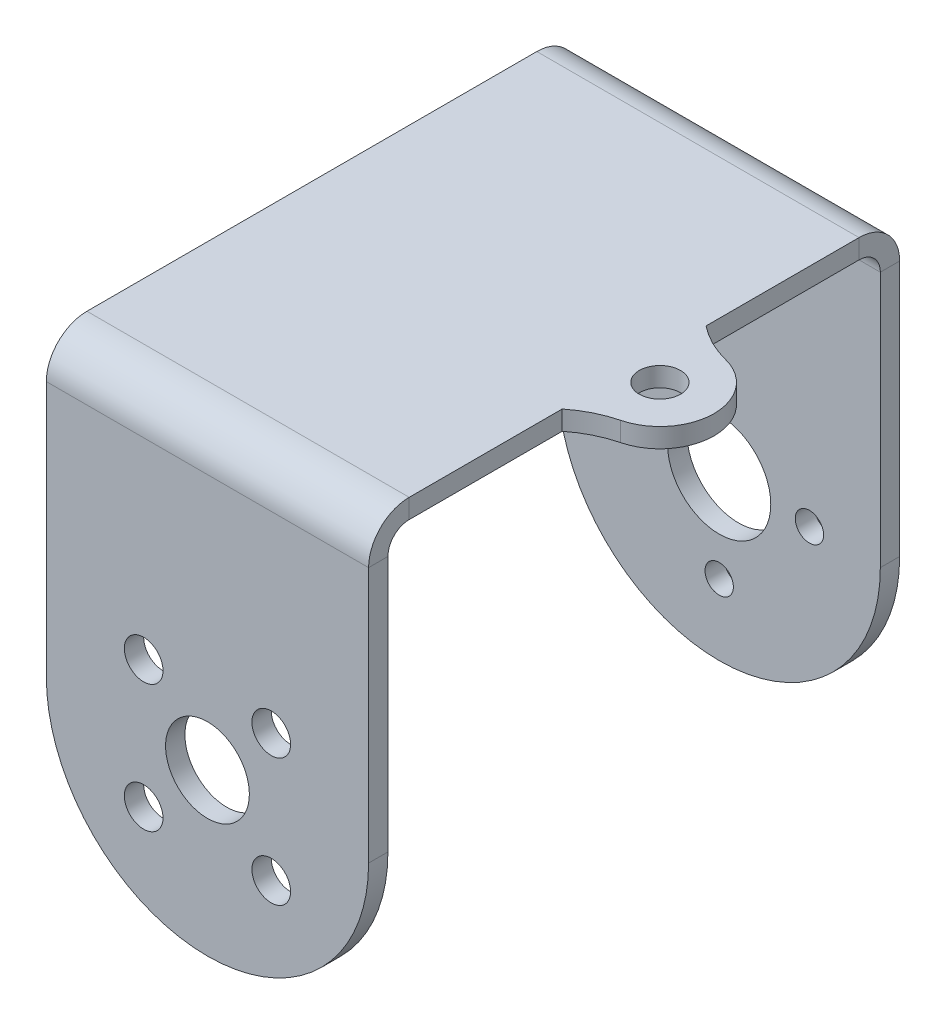
SolidWorks part; units mm, degrees
note: The reader was unsure of these and kept them because the rebuilt part matched: flange length of "Edge-Flange1".
material "1.0037 (S235JR)"
ref_plane "Front Plane" through (0, 0, 0) normal (0, 0, 1) x (1, 0, 0)
ref_plane "Top Plane" through (0, 0, 0) normal (0, 1, 0) x (1, 0, 0)
ref_plane "Right Plane" through (0, 0, 0) normal (1, 0, 0) x (0, 0, -1)
sketch "Sketch1" plane through (0, 0, 0) normal (0, 1, 0) x (1, 0, 0)
  line L1 (12.5, -19.1) -> (-12.5, -19.1)
  line L2 (12.5, -19.1) -> (12.5, 19.1)
  line L3 (12.5, 19.1) -> (-12.5, 19.1)
  line L4 (-12.5, -19.1) -> (-12.5, 19.1)
  line L5 (12.5, -19.1) -> (-12.5, 19.1) construction
  line L6 (12.5, 19.1) -> (-12.5, -19.1) construction
  point P0 (0, 0)
  dimension "D1" = 38.2
  dimension "D2" = 25
base flange "Base-Flange1" sketch "Sketch1" thickness 1.5 reverse thickness direction no parameters "D1"=1.65
edge flange "Edge-Flange1" sketch "Sketch10" flange profiles "Sketch10", "Sketch11" flange angle 90 flange length 34 flange position material outside bend radius 1.65 thickness 1.5 relief rectangular parameters "D6"=10, "D8"=1
sketch "Sketch10" plane through (0, -1.5, 19.1) normal (0, 0, 1) x (-1, 0, 0)
  line L0 (12.5, 0) -> (-12.5, 0) construction
  line L1 (12.5, 0) -> (-12.5, 0)
  line L2 (-12.5, 0) -> (-12.5, 34)
  line L3 (-12.5, 34) -> (12.5, 34)
  line L4 (12.5, 34) -> (12.5, 0)
sketch "Sketch11" plane through (0, -1.5, -19.1) normal (0, 0, -1) x (1, 0, 0)
  line L0 (12.5, 0) -> (-12.5, 0) construction
  line L1 (12.5, 0) -> (-12.5, 0)
  line L2 (-12.5, 0) -> (-12.5, 34)
  line L3 (-12.5, 34) -> (12.5, 34)
  line L4 (12.5, 34) -> (12.5, 0)
bend "EdgeBend1" bend radius 1.65 bend angle 90 parameters "D5"=1
bend "EdgeBend2" bend radius 1.65 bend angle 90 parameters "D5"=2
sketch "Sketch12" plane through (0, 0, 20.6) normal (0, 0, 1) x (1, 0, 0)
  line L0 (-12.5, -35.5) -> (12.5, -35.5) construction
  line L1 (4.9497, -27.9497) -> (-4.9497, -27.9497) construction
  line L2 (4.9497, -27.9497) -> (4.9497, -18.0503) construction
  line L3 (4.9497, -18.0503) -> (-4.9497, -18.0503) construction
  line L4 (-4.9497, -27.9497) -> (-4.9497, -18.0503) construction
  line L5 (4.9497, -27.9497) -> (-4.9497, -18.0503) construction
  line L6 (4.9497, -18.0503) -> (-4.9497, -27.9497) construction
  circle A0 centre (-4.9497, -18.0503) radius 1.5
  circle A1 centre (4.9497, -18.0503) radius 1.5
  circle A2 centre (-4.9497, -27.9497) radius 1.5
  circle A3 centre (4.9497, -27.9497) radius 1.5
  circle A4 centre (0, -23) radius 3.25
  point P0 (0, -23)
  point P7 (0, -35.5)
  dimension "D3" = 3
  dimension "D4" = 6.5
  dimension "D1" = 14
  dimension "D2" = 12.5
extrude "Cut-Extrude1" cut sketch "Sketch12" against normal up to next normal cut yes
sketch "Sketch13" plane through (0, 0, -20.6) normal (0, 0, -1) x (-1, 0, 0)
  line L0 (0, -23) -> (0, -30) construction
  line L1 (0, -23) -> (-7, -23) construction
  line L2 (0, -23) -> (0, -16) construction
  line L3 (0, -23) -> (7, -23) construction
  circle A0 centre (0, -23) radius 4
  circle A1 centre (0, -30) radius 1.1
  circle A2 centre (-7, -23) radius 1.1
  circle A3 centre (0, -16) radius 1.1
  circle A4 centre (7, -23) radius 1.1
  point P12 (0, -23)
  dimension "D1" = 8
  dimension "D3" = 2.2
  dimension "D2" = 7
  dimension "D4" = 4
extrude "Cut-Extrude2" cut sketch "Sketch13" against normal up to next normal cut yes
fillet "Fillet1" radius 12.5 4 edges at (12.5, -35.5, 19.85) (-12.5, -35.5, 19.85) (-12.5, -35.5, -19.85) (12.5, -35.5, -19.85)
sketch "Sketch14" plane through (0, -1.5, 0) normal (0, -1, 0) x (1, 0, 0)
  line L0 (12.5, -5.5817) -> (12.5, 5.5817)
  line L1 (12.5, 17.45) -> (12.5, -17.45) construction
  arc A0 (9.5, 11.8267) -> (15.533, 4.0723) centre (17.5, 11.8267) ccw construction
  arc A1 (15.533, -4.0723) -> (9.5, -11.8267) centre (17.5, -11.8267) ccw construction
  arc A2 (15.533, -4.0723) -> (15.533, 4.0723) centre (14.5, 0) ccw construction
  arc A3 (12.5, 5.5817) -> (15.533, 4.0723) centre (17.5, 11.8267) ccw
  arc A4 (15.533, -4.0723) -> (12.5, -5.5817) centre (17.5, -11.8267) ccw
  arc A5 (15.533, -4.0723) -> (15.533, 4.0723) centre (14.5, 0) ccw
  circle A6 centre (14.5, 0) radius 1.6 construction
  circle A7 centre (14.5, 0) radius 1.6
base flange "Tab1" sketch "Sketch14" thickness 1.5 reverse thickness direction no parameters "D1"=1.65
sketch "Bend-Lines1" [suppressed] plane through (0, 0, 0) normal (0, 1, 0) x (1, 0, 0)
sketch "Bounding-Box1" [suppressed] plane through (0, 0, 0) normal (0, 1, 0) x (1, 0, 0)
sheet metal parameters "Sheet-Metal1" thickness 1.5 parameters "D1"=2
flat pattern "Flat-Pattern1" [suppressed]
sketch "Bend-Lines2" plane through (0, 0, 0) normal (0, 1, 0) x (1, 0, 0)
sketch3d "Bounding-Box2" [suppressed]
  line L0 (10, 26.25, 0) -> (10, -26.25, 0) construction
  line L1 (-10, 26.25, 0) -> (-10, -26.25, 0) construction
  line L2 (10, 26.25, 0) -> (-10, 26.25, 0) construction
  line L3 (10, -26.25, 0) -> (-10, -26.25, 0) construction
sheet metal parameters "Sheet-Metal2" thickness 1.5 parameters "D1"=2
flat pattern "Flat-Pattern1"
sketch "Bend-Lines2" plane through (0, 0, 0) normal (0, 1, 0) x (1, 0, 0)
  line L0 (10, 26.4098) -> (-10, 26.4098) construction
  line L1 (-10, -26.4098) -> (10, -26.4098) construction
  line L2 (10, 26.4098) -> (-10, 26.4098) construction
  line L3 (-10, -26.4098) -> (10, -26.4098) construction
sketch3d "Bounding-Box2" [suppressed]
  line L0 (-10, 46.5697, 0) -> (-10, -46.5697, 0) construction
  line L1 (10, 46.5697, 0) -> (10, -46.5697, 0) construction
  line L2 (-10, 46.5697, 0) -> (10, 46.5697, 0) construction
  line L3 (-10, -46.5697, 0) -> (10, -46.5697, 0) construction
bend of the flat pattern "EdgeBend1>1"
bend of the flat pattern "EdgeBend2>1"
sheet metal parameters "Sheet-Metal3" thickness 1.5 parameters "D1"=2
flat pattern "Flat-Pattern1"
sketch "Bend-Lines2" plane through (0, 0, 0) normal (0, 1, 0) x (1, 0, 0)
  line L0 (10, 26.4098) -> (-10, 26.4098) construction
  line L1 (-10, -26.4098) -> (10, -26.4098) construction
  line L2 (10, 26.4098) -> (-10, 26.4098) construction
  line L3 (-10, -26.4098) -> (10, -26.4098) construction
sketch3d "Bounding-Box2" [suppressed]
  line L0 (-10, 51.5697, 0) -> (-10, -51.5697, 0) construction
  line L1 (10, 51.5697, 0) -> (10, -51.5697, 0) construction
  line L2 (-10, 51.5697, 0) -> (10, 51.5697, 0) construction
  line L3 (-10, -51.5697, 0) -> (10, -51.5697, 0) construction
bend of the flat pattern "EdgeBend1>1"
bend of the flat pattern "EdgeBend2>1"
sheet metal parameters "Sheet-Metal4" thickness 1.5 parameters "D1"=2
flat pattern "Flat-Pattern1"
sketch "Bend-Lines2" plane through (0, 0, 0) normal (0, 1, 0) x (1, 0, 0)
  line L0 (12.5, 19.085) -> (-12.5, 19.085) construction
  line L1 (-12.5, -19.085) -> (12.5, -19.085) construction
  line L2 (12.5, 19.085) -> (-12.5, 19.085) construction
  line L3 (-12.5, -19.085) -> (12.5, -19.085) construction
sketch3d "Bounding-Box2" [suppressed]
  line L0 (-12.5, 53.3199, 0) -> (-12.5, -53.3199, 0) construction
  line L1 (12.5, 53.3199, 0) -> (12.5, -53.3199, 0) construction
  line L2 (-12.5, 53.3199, 0) -> (12.5, 53.3199, 0) construction
  line L3 (-12.5, -53.3199, 0) -> (12.5, -53.3199, 0) construction
bend of the flat pattern "EdgeBend1>1"
bend of the flat pattern "EdgeBend2>1"
sheet metal parameters "Sheet-Metal7" thickness 1.5 parameters "D1"=2
flat pattern "Flat-Pattern7"
sketch "Bend-Lines3" plane through (0, 0, 0) normal (0, 1, 0) x (1, 0, 0)
  line L0 (12.5, 19.335) -> (-12.5, 19.335) construction
  line L1 (-12.5, -19.335) -> (12.5, -19.335) construction
  line L2 (12.5, 19.335) -> (-12.5, 19.335) construction
  line L3 (-12.5, -19.335) -> (12.5, -19.335) construction
sketch3d "Bounding-Box3" [suppressed]
  line L0 (-12.5, 53.5699, 0) -> (-12.5, -53.5699, 0) construction
  line L1 (18.701, 53.5699, 0) -> (18.701, -53.5699, 0) construction
  line L2 (-12.5, 53.5699, 0) -> (18.701, 53.5699, 0) construction
  line L3 (-12.5, -53.5699, 0) -> (18.701, -53.5699, 0) construction
bend of the flat pattern "EdgeBend2>2"
bend of the flat pattern "EdgeBend1>2"
